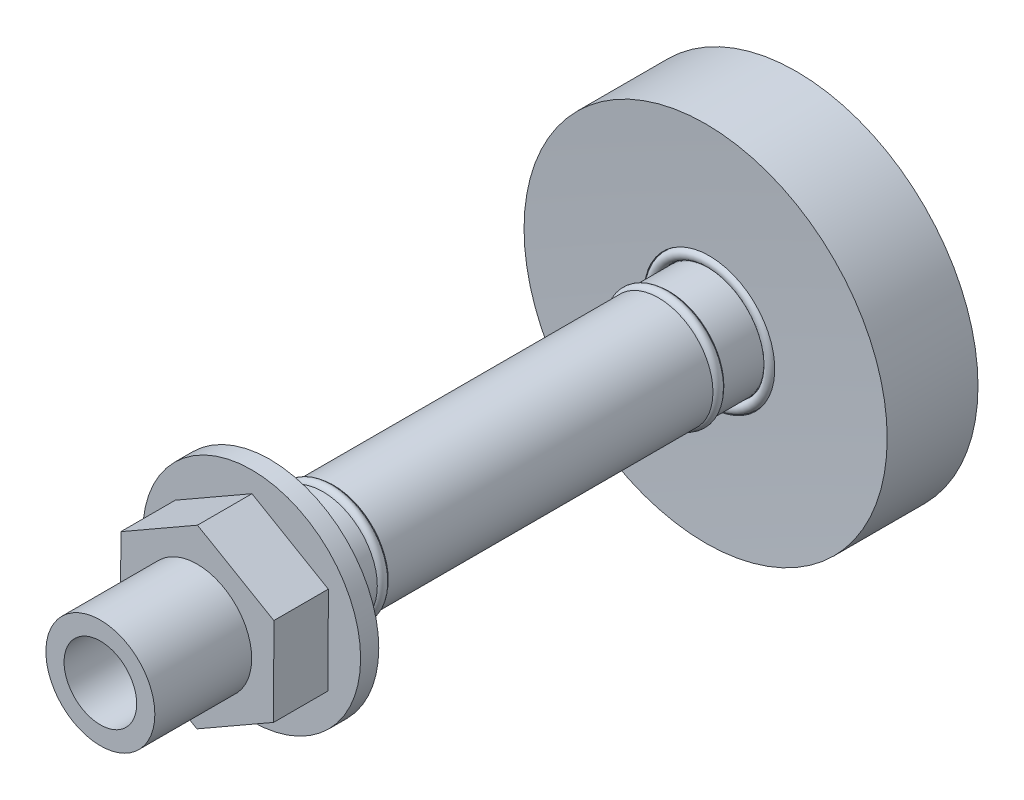
SolidWorks part; units mm, degrees
ref_plane "Front Plane" through (0, 0, 0) normal (0, 0, 1) x (1, 0, 0)
ref_plane "Top Plane" through (0, 0, 0) normal (0, 1, 0) x (1, 0, 0)
ref_plane "Right Plane" through (0, 0, 0) normal (1, 0, 0) x (0, 0, -1)
sketch "Sketch2" plane through (0, 0, 0) normal (1, 0, 0) x (0, 0, -1)
  line L0 (-82.8882, 0) -> (83.7577, 0) construction
  line L1 (-68.6871, 10) -> (-54.1961, 10)
  line L2 (-54.1961, 10) -> (-54.1961, 5.2)
  line L3 (-54.1961, 5.2) -> (49.3573, 5.2)
  line L4 (49.3573, 5.2) -> (49.3573, 10)
  line L5 (49.3573, 10) -> (89.3573, 10)
  line L6 (89.3573, 10) -> (89.3573, 50)
  line L7 (89.3573, 50) -> (64.3573, 50)
  line L9 (64.6949, 15) -> (-55.3051, 15)
  line L11 (-55.6427, 30) -> (-75.6427, 30)
  line L12 (-75.6427, 30) -> (-75.6427, 15)
  line L13 (-75.6427, 15) -> (-102.3061, 15)
  line L14 (-102.3061, 15) -> (-102.3061, 10)
  line L15 (-102.3061, 10) -> (-68.6871, 10)
  line L16 (64.6949, 15) -> (65.431, 15)
  arc A0 (-55.3051, 15) -> (-55.6427, 30) centre (-1055.1926, 0) ccw
  arc A1 (65.431, 15) -> (64.3573, 50) centre (-994.4628, 0) ccw
  dimension "D14" = 2000
  dimension "D12" = 2120
  dimension "D2" = 5.2
  dimension "D3" = 10
  dimension "D4" = 10
  dimension "D5" = 5
  dimension "D6" = 30
  dimension "D7" = 50
  dimension "D8" = 40
  dimension "D9" = 15
  dimension "D10" = 20
  dimension "D11" = 25
  dimension "D13" = 120
revolve "Revolve1" add sketch "Sketch2" angle 360 about L0
sketch "Sketch3" plane through (0, 0, 0) normal (0, 1, 0) x (1, 0, 0)
  line L1 (9.7804, 61.4892) -> (4.7804, 61.4892)
  line L2 (9.7804, 61.4892) -> (9.7804, 49.4892)
  line L3 (9.7804, 49.4892) -> (4.7804, 49.4892)
  line L4 (4.7804, 61.4892) -> (4.7804, 49.4892)
  line L5 (0, 27.0222) -> (0, -36.1697) construction
  line L6 (9.9377, -54.2645) -> (4.9377, -54.2645)
  line L7 (9.9377, -54.2645) -> (9.9377, -66.2645)
  line L8 (9.9377, -66.2645) -> (4.9377, -66.2645)
  line L9 (4.9377, -54.2645) -> (4.9377, -66.2645)
  dimension "D1" = 5
  dimension "D2" = 12
  dimension "D3" = 5
  dimension "D4" = 12
revolve "Revolve2" add sketch "Sketch3" angle 360 about L5
sketch "Sketch4" plane through (0, 0, 0) normal (0, 1, 0) x (1, 0, 0)
  line L1 (5.1844, 46.1353) -> (7.1844, 46.1342)
  line L2 (5.1844, 46.1353) -> (5.1844, 43.1342)
  line L3 (5.1844, 43.1342) -> (7.1844, 43.1342)
  line L4 (7.1844, 46.1342) -> (7.1844, 43.1342)
  line L5 (5.1671, -46.0486) -> (7.1671, -46.0486)
  line L6 (5.1671, -46.0486) -> (5.1671, -49.0486)
  line L7 (5.1671, -49.0486) -> (7.1671, -49.0486)
  line L8 (7.1671, -46.0486) -> (7.1671, -49.0486)
  line L14 (15.0008, 54.3777) -> (13.0008, 54.3777)
  line L15 (15.0008, 54.3777) -> (15.0008, 51.3777)
  line L16 (15.0008, 51.3777) -> (13.0008, 51.3777)
  line L17 (13.0008, 54.3777) -> (13.0008, 51.3777)
  line L23 (0, 31.3382) -> (0, -16.0514) construction
  line L24 (15.0082, -38.0516) -> (13.0082, -38.0516)
  line L25 (15.0082, -38.0516) -> (15.0082, -41.0516)
  line L26 (15.0082, -41.0516) -> (13.0082, -41.0516)
  line L27 (13.0082, -38.0516) -> (13.0082, -41.0516)
  line L28 (14.9998, -55.3051) -> (17.9998, -55.3051)
  line L34 (14.9998, -55.3051) -> (14.9998, -57.3051)
  line L35 (14.9998, -57.3051) -> (17.9998, -57.3051)
  line L36 (17.9998, -55.3051) -> (17.9998, -57.3051)
  line L38 (15.0065, 65.3648) -> (18.0065, 65.3648)
  line L39 (15.0065, 65.3648) -> (15.0065, 67.3648)
  line L40 (15.0065, 67.3648) -> (18.0065, 67.3648)
  line L41 (18.0065, 65.3648) -> (18.0065, 67.3648)
  dimension "D1" = 3
  dimension "D2" = 2
  dimension "D3" = 2
  dimension "D4" = 3
  dimension "D5" = 2
  dimension "D6" = 3
  dimension "D7" = 2
  dimension "D8" = 3
  dimension "D9" = 2
  dimension "D10" = 3
  dimension "D11" = 2
  dimension "D12" = 3
revolve "Cut-Revolve1" cut sketch "Sketch4" angle 360 about L23
sketch "Sketch5" plane through (0, 0, 0) normal (0, 1, 0) x (1, 0, 0)
  line L0 (0, 40.6102) -> (0, 26.4444) construction
  circle A0 centre (16.501, 65.8942) radius 1.4
  circle A1 centre (14.4375, 52.8864) radius 1.4
  circle A2 centre (5.7322, 44.6572) radius 1.4
  circle A3 centre (14.4375, -39.5674) radius 1.4
  circle A4 centre (5.7322, -47.5621) radius 1.4
  circle A5 centre (16.501, -55.8575) radius 1.4
  dimension "D1" = 2.8
  dimension "D2" = 2.8
  dimension "D3" = 2.8
  dimension "D4" = 2.8
  dimension "D5" = 2.8
  dimension "D6" = 2.8
revolve "Revolve3" add sketch "Sketch5" angle 360 about L0
sketch "Sketch6" plane through (0, 0, 75.6427) normal (0, 0, 1) x (1, 0, 0)
  line L0 (0, 0) -> (21.0689, -0.0664) construction
  line L1 (21.0306, -12.2305) -> (21.1072, 12.0977)
  line L2 (21.1072, 12.0977) -> (0.0767, 24.3283)
  line L3 (0.0767, 24.3283) -> (-21.0306, 12.2305)
  line L4 (-21.0306, 12.2305) -> (-21.1072, -12.0977)
  line L5 (-21.1072, -12.0977) -> (-0.0767, -24.3283)
  line L6 (-0.0767, -24.3283) -> (21.0306, -12.2305)
  line L7 (0, 0) -> (21.1072, 12.0977) construction
  circle A0 centre (0, 0) radius 21.069 construction
  circle A1 centre (0, 0) radius 30
extrude "Cut-Extrude1" cut sketch "Sketch6" against normal blind 15
equation "\"mountAngle\" = 30deg"
equation "\"ThrusterDim\"= 140mm"
equation "\"hatchHoleDiameter\"= 600mm"
equation "\"hullThickness\"= 120mm"
equation "\"gasketHullInterconnectWidth\"= 100mm"
equation "\"collarThickness\"= 15"
equation "\"hatchTunnelLength\"=200"
equation "\"oRingDiameter\"=2"
equation "\"boltPatternRadiusInterconnect\"=500"
equation "\"interconnectBoltDiameter\"=30"
equation "\"hatchShaftDiameter\"=20"
equation "\"hatchMinima\"=50"
equation "\"hullDiameter\"=2000"
equation "\"hatchMaxima\"=180"
equation "\"bushingFlatHatch\"=15"
equation "\"hingePivotDiameter\"=20"
equation "\"handleWidth\"=250"
equation "\"handleHeight\"=160"
equation "\"handleThickness\"=25"
equation "\"FrameLength\"= 4300"
equation "\"FrameMidLength\"= 3000"
equation "\"TubeOD\"= 100"
equation "\"FrameBackFlat\"= 800"
equation "\"TubeWall\"=15"
equation "\"TopMemberAngle\"=120"
equation "\"FrameHight\"= 2500"
equation "\"D12@Sketch2\"=\"hullThickness\" + \"hullDiameter\""
equation "\"D13@Sketch2\"=\"hullThickness\""
